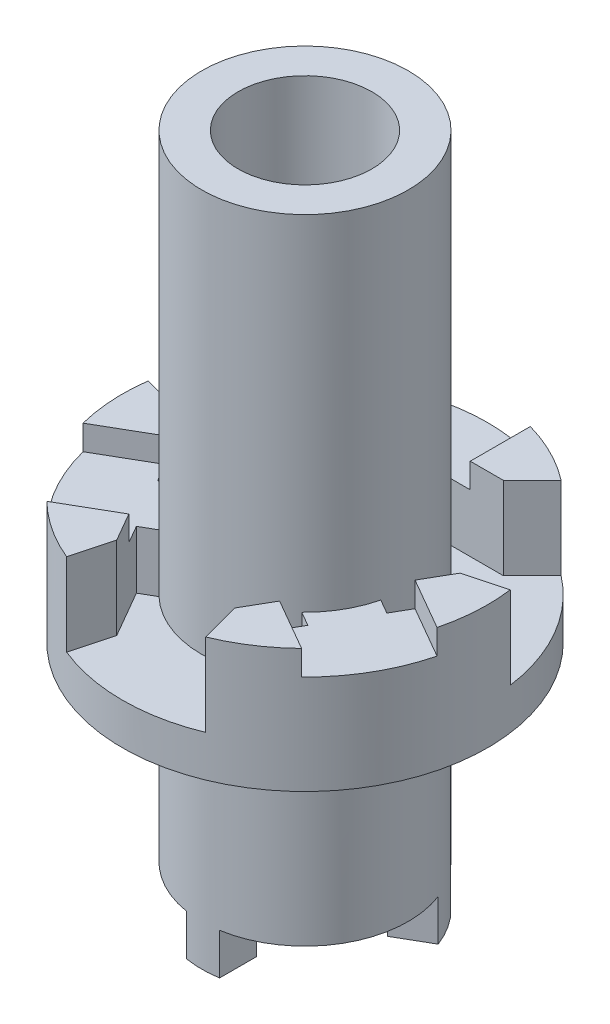
SolidWorks part; units mm, degrees
material "Nylon 6/10"
ref_plane "Front Plane" through (0, 0, 0) normal (0, 0, 1) x (1, 0, 0)
ref_plane "Top Plane" through (0, 0, 0) normal (0, 1, 0) x (1, 0, 0)
ref_plane "Right Plane" through (0, 0, 0) normal (1, 0, 0) x (0, 0, -1)
sketch "Sketch1" plane through (0, 0, 0) normal (0, 0, 1) x (1, 0, 0)
  line L0 (-1.0287, 0) -> (-1.0287, 9.7384)
  line L1 (-1.0287, 9.7384) -> (-1.5875, 9.7384)
  line L2 (-1.5875, 9.7384) -> (-1.5875, 3.556)
  line L3 (-1.5875, 3.556) -> (-2.8067, 3.556)
  line L4 (-2.8067, 3.556) -> (-2.8067, 2.921)
  line L5 (-2.8067, 2.921) -> (-1.5875, 2.921)
  line L6 (-1.5875, 2.921) -> (-1.5875, 0)
  line L7 (-1.5875, 0) -> (-1.0287, 0)
  line L8 (0, 0) -> (0, 13.8673)
  line L9 (0, 0) -> (-1.0287, 0)
  dimension "D1" = 9.7384
  dimension "D2" = 2.921
  dimension "D3" = 1.0287
  dimension "D4" = 0.5588
  dimension "D5" = 2.8067
  dimension "D6" = 0.635
revolve "Revolve1" add sketch "Sketch1" angle 360 about L8 region at (-1.4188, 4.6661, 0)
sketch "Sketch2" plane through (0, 3.556, 0) normal (0, 1, 0) x (1, 0, 0)
  line L0 (-0.4445, 1.524) -> (-0.4445, 1.778)
  line L1 (0.4445, 1.524) -> (0.4445, 1.778)
  line L2 (-0.4445, 1.778) -> (-1.27, 1.778)
  line L3 (-1.27, 1.778) -> (-1.7143, 2.2223)
  line L4 (0.4445, 1.778) -> (1.27, 1.778)
  line L5 (1.27, 1.778) -> (1.7143, 2.2223)
  circle A0 centre (0, 0) radius 1.5875 construction
  arc A1 (-1.7143, 2.2223) -> (1.7143, 2.2223) centre (0, 0) cw
  circle A2 centre (0, 0) radius 2.8067 construction
  arc A3 (0.4445, 1.524) -> (-0.4445, 1.524) centre (0, 0) ccw
  dimension "D6" = 2.8067
  dimension "D8" = 1.5875
  dimension "D1" = 0.889
  dimension "D2" = 0.4445
  dimension "D3" = 1.778
  dimension "D4" = 45
  dimension "D5" = 45
  dimension "D7" = 2.54
extrude "Boss-Extrude1" add sketch "Sketch2" along normal blind 1.27
sketch "Sketch4" plane through (0, 4.826, 0) normal (0, 1, 0) x (1, 0, 0)
  line L0 (-0.762, 1.3927) -> (-0.762, 2.7013)
  line L1 (0.762, 1.3927) -> (0.762, 2.7013)
  circle A0 centre (0, 0) radius 1.5875 construction
  arc A1 (1.7143, 2.2223) -> (-1.7143, 2.2223) centre (0, 0) ccw construction
  arc A2 (-0.762, 2.7013) -> (0.762, 2.7013) centre (0, 0) cw
  arc A3 (0.762, 1.3927) -> (-0.762, 1.3927) centre (0, 0) ccw
  dimension "D1" = 1.524
  dimension "D2" = 0.762
extrude "Cut-Extrude1" cut sketch "Sketch4" against normal blind 0.381
pattern_circular "CirPattern1" count 3 over 360 of "Boss-Extrude1", "Cut-Extrude1"
chamfer "Chamfer1" distance 0.381 angle 45 1 edges at (0, 2.921, -1.5875)
sketch "Sketch3" plane through (0, 0, 0) normal (0, -1, 0) x (1, 0, 0)
  line L0 (0.254, 1.567) -> (0.254, 0.9968)
  line L1 (-0.254, 1.567) -> (-0.254, 0.9968)
  circle A0 centre (0, 0) radius 1.5875 construction
  circle A1 centre (0, 0) radius 1.0287 construction
  arc A2 (0.254, 0.9968) -> (-0.254, 0.9968) centre (0, 0) ccw
  arc A3 (0.254, 1.567) -> (-0.254, 1.567) centre (0, 0) ccw
  dimension "D3" = 1.0287
  dimension "D4" = 1.5875
  dimension "D1" = 0.508
  dimension "D2" = 0.254
extrude "Boss-Extrude2" add sketch "Sketch3" along normal blind 0.635
pattern_circular "CirPattern2" count 3 over 360 about axis through (0, -0.635, 0) along (0, 1, 0) of "Boss-Extrude2"
